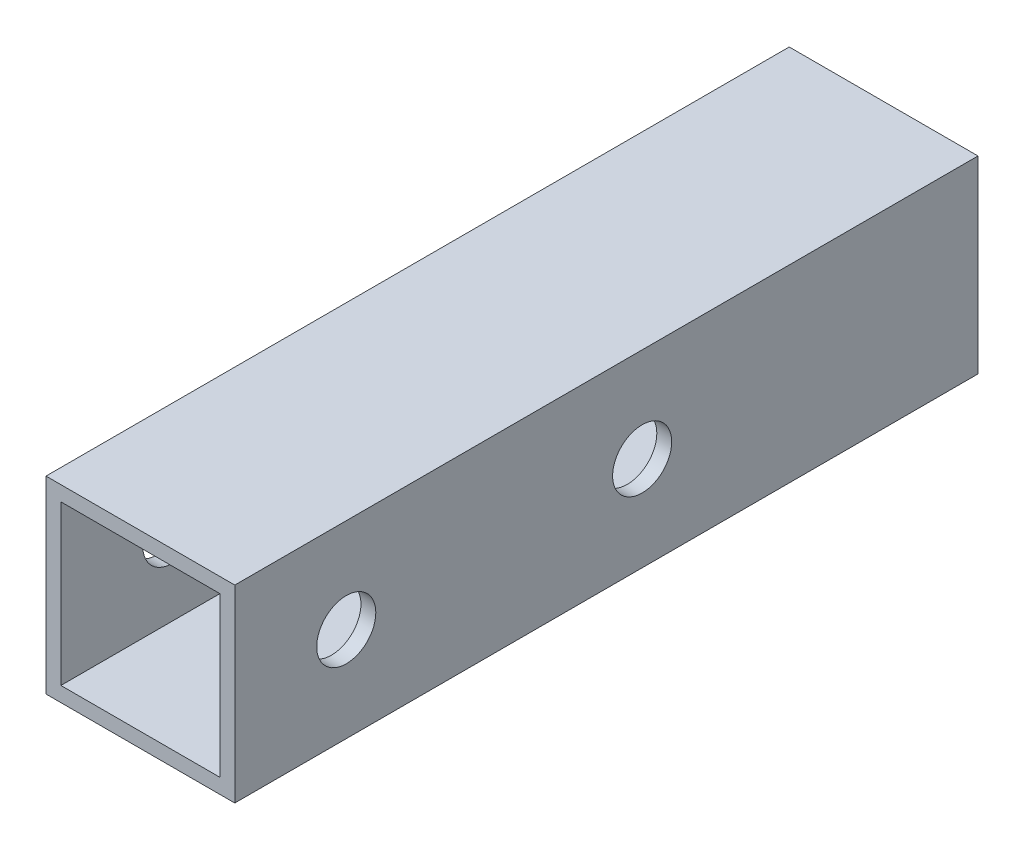
SolidWorks part; units mm, degrees
material "Acrylic (Medium-high impact)"
ref_plane "Front Plane" through (0, 0, 0) normal (0, 0, 1) x (1, 0, 0)
ref_plane "Top Plane" through (0, 0, 0) normal (0, 1, 0) x (1, 0, 0)
ref_plane "Right Plane" through (0, 0, 0) normal (1, 0, 0) x (0, 0, -1)
sketch "Sketch1" plane through (0, 0, 0) normal (0, 0, 1) x (1, 0, 0)
  line L1 (0, 0) -> (25.4, 0)
  line L2 (0, 0) -> (0, 25.4)
  line L3 (0, 25.4) -> (25.4, 25.4)
  line L4 (25.4, 0) -> (25.4, 25.4)
  line L5 (2, 23.4) -> (23.4, 23.4)
  line L6 (2, 23.4) -> (2, 2)
  line L7 (2, 2) -> (23.4, 2)
  line L8 (23.4, 23.4) -> (23.4, 2)
  dimension "D1" = 25.4
  dimension "D2" = 25.4
  dimension "D3" = 2
  dimension "D4" = 2
  dimension "D5" = 2
  dimension "D6" = 2
extrude "Boss-Extrude1" add sketch "Sketch1" along normal blind 100
sketch "Sketch2" plane through (25.4, 0, 0) normal (1, 0, 0) x (0, 0, -1)
  line L0 (0, 12.7) -> (-100, 12.7) construction
  line L1 (0, 0) -> (0, 25.4) construction
  line L2 (-100, 0) -> (-100, 25.4) construction
  circle A0 centre (-85, 12.7) radius 3.975
  circle A1 centre (-45.19, 12.7) radius 3.975
  dimension "D1" = 7.95
  dimension "D3" = 7.95
  dimension "D2" = 15
  dimension "D4" = 39.81
extrude "Cut-Extrude1" cut sketch "Sketch2" against normal blind 50
sketch "Sketch3" plane through (0, 0, 0) normal (0, -1, 0) x (1, 0, 0)
  line L0 (25.4, 100) -> (25.4, 0) construction
  line L1 (0, 0) -> (25.4, 0) construction
  line L2 (8.45, 70) -> (8.45, 10)
  line L3 (5.35, 10) -> (5.35, 70)
  circle A0 centre (6.9, 70) radius 1.55
  circle A1 centre (6.9, 10) radius 1.55
  dimension "D2" = 3.1
  dimension "D3" = 3.1
  dimension "D1" = 18.5
  dimension "D4" = 18.5
  dimension "D5" = 60
  dimension "D6" = 10
extrude "Cut-Extrude4" cut sketch "Sketch3" against normal blind 10 contours A1 L2 A0 L3 | A1 | A0 region at (6.9, 0, 70) region at (6.9, 0, 40) region at (6.9, 0, 10)
sketch "Sketch4" plane through (0, 0, 0) normal (0, -1, 0) x (1, 0, 0)
  line L0 (0, 0) -> (25.4, 0) construction
  circle A0 centre (7.5, 2.7657) radius 1.778
  circle A1 centre (17.5, 2.7657) radius 1.778
  dimension "D1" = 10
  dimension "D3" = 2.7657
  dimension "D2" = 2.7657
extrude "Cut-Extrude5" cut sketch "Sketch4" against normal blind 10
